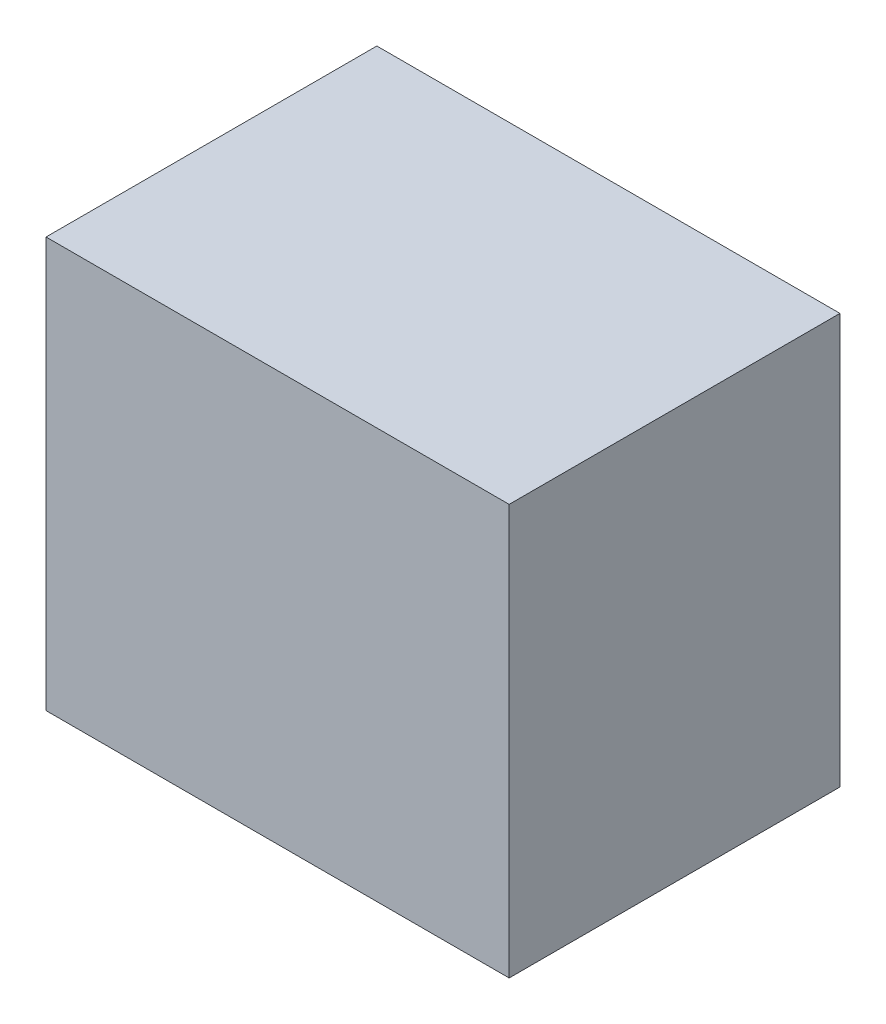
SolidWorks part; units mm, degrees
ref_plane "Спереди" through (0, 0, 0) normal (0, 0, 1) x (1, 0, 0)
ref_plane "Сверху" through (0, 0, 0) normal (0, 1, 0) x (1, 0, 0)
ref_plane "Справа" through (0, 0, 0) normal (1, 0, 0) x (0, 0, -1)
sketch "Эскиз2" plane through (0, 0, 0) normal (0, 1, 0) x (1, 0, 0)
  line L1 (0, 0) -> (350, 0)
  line L2 (0, 0) -> (0, 250)
  line L3 (0, 250) -> (350, 250)
  line L4 (350, 0) -> (350, 250)
extrude "Бобышка-Вытянуть1" add sketch "Эскиз2" along normal blind 310
